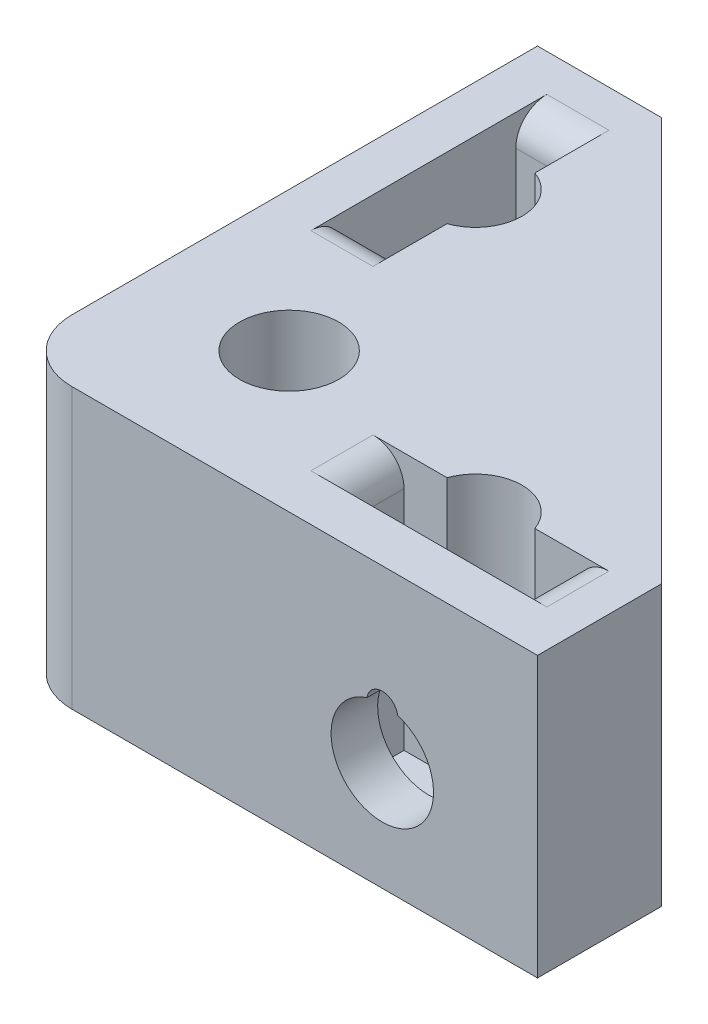
SolidWorks part; units mm, degrees
ref_plane "Front Plane" through (0, 0, 0) normal (0, 0, 1) x (1, 0, 0)
ref_plane "Top Plane" through (0, 0, 0) normal (0, 1, 0) x (1, 0, 0)
ref_plane "Right Plane" through (0, 0, 0) normal (1, 0, 0) x (0, 0, -1)
sketch "Sketch1" plane through (0, 0, 0) normal (0, 1, 0) x (1, 0, 0)
  line L2 (10.5, 10.5) -> (17, 4)
  line L3 (17, 4) -> (17, 0)
  line L4 (17, 0) -> (0, 0)
  line L5 (0, 0) -> (10.5, 10.5)
  point P1 (14, 0)
  dimension "D1" = 45
  dimension "D2" = 17
  dimension "D3" = 4
extrude "Boss-Extrude1" add sketch "Sketch1" along normal blind 9
sketch "Sketch2" plane through (0, 9, 0) normal (0, 1, 0) x (1, 0, 0)
  line L0 (0, 0) -> (35355.3391, 35355.3391) construction
  line L9 (0, 0) -> (17, 0) construction
  line L12 (9.2, 1.5) -> (9.2, 3.5)
  line L13 (14.8, 3.5) -> (9.2, 3.5)
  line L14 (14.8, 1.5) -> (14.8, 3.5)
  line L15 (14.8, 1.5) -> (9.2, 1.5)
  line L16 (0, 0) -> (17, 0) construction
  point P4 (11, 3.5)
  point P5 (12, 3.5)
  point P6 (0, 0)
  dimension "D1" = 45
  dimension "D2" = 12
  dimension "D6" = 1.5
  dimension "D8" = 2
  dimension "D9" = 5.6
extrude "Cut-Extrude1" cut sketch "Sketch2" against normal offset from surface (8.3 mm away) 0.7 up to face at (11.125, 0, -3.625)
sketch "Sketch4" plane through (0, 0, 0) normal (0, 0, 1) x (1, 0, 0)
  line L0 (12, 3.5) -> (14.8, 3.5) construction
  line L1 (12, 3.5) -> (12, 0.7) construction
  line L4 (14.8, 0.7) -> (14.8, 9)
  line L5 (14.8, 9) -> (9.2, 9)
  line L6 (9.2, 9) -> (9.2, 0.7)
  line L7 (9.2, 0.7) -> (14.8, 0.7)
  line L8 (14.8, 0.7) -> (14.8, 9) construction
  line L9 (14.8, 9) -> (9.2, 9) construction
  line L10 (9.2, 9) -> (9.2, 0.7) construction
  line L11 (9.2, 0.7) -> (14.8, 0.7) construction
  arc A0 (11.5055, 5.0742) -> (12.4945, 5.0742) centre (12, 3.5) ccw
  arc A1 (12.4945, 5.0742) -> (11.5055, 5.0742) centre (12, 5) ccw
  point P9 (0, 0)
  point P10 (12, 3.5)
  dimension "D1" = 3.3
  dimension "D3" = 1
  dimension "D4" = 0.15
  dimension "D2" = 0
extrude "Cut-Extrude2" cut sketch "Sketch4" against normal through all
sketch "Sketch16" plane through (0, 9, 0) normal (0, 1, 0) x (1, 0, 0)
  line L0 (9.2, 1.5) -> (14.8, 1.5) construction
  line L1 (14.8, 3.5) -> (9.2, 3.5) construction
  circle A0 centre (12, 3) radius 1.5
  point P4 (12, 3.5)
  point P5 (0, 0)
  dimension "D1" = 3
extrude "Cut-Extrude5" cut sketch "Sketch16" against normal up to next
fillet "Fillet2" radius 1 2 edges at (9.2, 9, -2.5) (14.8, 9, -2.5)
sketch "Sketch6" plane through (0, 9, 0) normal (0, 1, 0) x (1, 0, 0)
  line L0 (12, 1.5) -> (12, 6.8) construction
  line L1 (9.2, 1.5) -> (14.8, 1.5) construction
  line L2 (12, 1.5) -> (12, -3.2) construction
  line L3 (0, 0) -> (17, 0) construction
  line L5 (10.5, 10.5) -> (0, 0) construction
  circle A0 centre (4.5, 4.5) radius 1.6
  point P9 (5.1629, 5.1629)
  dimension "D3" = 3.2
  dimension "D1" = 3.2
  dimension "D2" = 10
  dimension "D4" = 4.5
extrude "Cut-Extrude3" cut sketch "Sketch6" against normal through all
sketch "Sketch9" plane through (0, 0, 0) normal (0, -1, 0) x (1, 0, 0)
  line L0 (3.3686, -3.3686) -> (0, 0) construction
  line L1 (7.5449, -5.3159) -> (6.729, -2.271)
  line L2 (6.729, -2.271) -> (3.6841, -1.4551)
  line L3 (3.6841, -1.4551) -> (1.4551, -3.6841)
  line L4 (1.4551, -3.6841) -> (2.271, -6.729)
  line L5 (2.271, -6.729) -> (5.3159, -7.5449)
  line L6 (5.3159, -7.5449) -> (7.5449, -5.3159)
  circle A0 centre (4.5, -4.5) radius 2.73 construction
  point P1 (3.6033, -1.4779)
  dimension "D1" = 5.46
extrude "Cut-Extrude4" cut sketch "Sketch9" against normal blind 3
fillet "Fillet3" radius 1 4 edges at (3.1269, 0, -2.0123) (5.2066, 0, -1.863) (7.137, 0, -3.7934) (6.9877, 0, -5.8731)
mirror "Mirror1" about plane through (0, 9, 0) normal (0.7071, 0, 0.7071) of bodies 106 103
fillet "Fillet1" radius 2 1 edges at (0, 4.5, 0)
